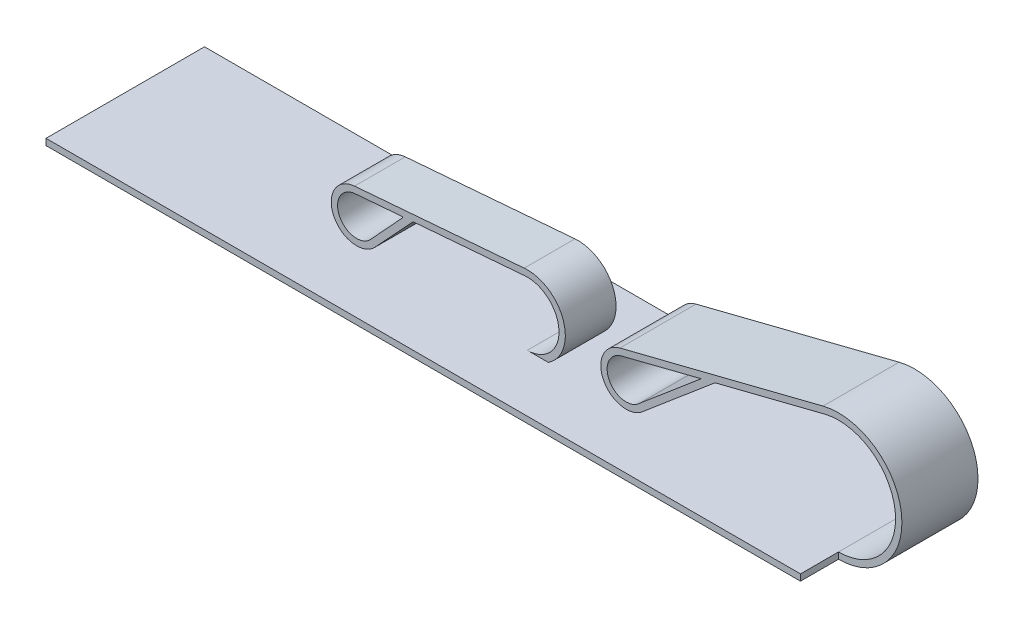
SolidWorks part; units mm, degrees
material "A-Glass Fiber"
ref_plane "Front" through (0, 0, 0) normal (0, 0, 1) x (1, 0, 0)
ref_plane "Top" through (0, 0, 0) normal (0, 1, 0) x (1, 0, 0)
ref_plane "Right" through (0, 0, 0) normal (1, 0, 0) x (0, 0, -1)
sketch "Sketch1" plane through (0, 0, 0) normal (0, 0, 1) x (1, 0, 0)
  line L0 (8.3294, 0) -> (75.2426, 0)
  line L1 (125.1284, 17.7267) -> (107.8556, 13.3703)
  line L2 (74.8373, 9.9835) -> (57.2359, 8.552)
  line L3 (50.5247, 2.7839) -> (55.5536, 8.2411)
  line L4 (95.9369, 4.6002) -> (105.6489, 12.8137)
  line L5 (74.7562, 10.9803) -> (47.9943, 8.8037)
  line L6 (57.2359, 8.552) -> (51.2601, 2.1062)
  line L7 (107.8556, 13.3703) -> (96.6378, 3.887)
  line L8 (8.3294, -1) -> (127.3294, -1)
  line L9 (124.8839, 18.6964) -> (92.8559, 10.6185)
  line L10 (75.2426, 0) -> (78.5593, 0)
  line L11 (127.3294, 0) -> (127.3294, -1)
  line L12 (78.5593, 0) -> (127.3294, 0)
  line L13 (105.6489, 12.8137) -> (93.1005, 9.6489)
  line L15 (55.4719, 8.4085) -> (48.0754, 7.807)
  line L16 (125.1284, 17.7267) -> (93.1005, 9.6489) construction
  line L17 (8.3294, 0) -> (8.3294, -1)
  line L21 (124.8839, 18.6964) -> (92.8559, 10.6185) construction
  arc A0 (127.3294, 0) -> (125.1284, 17.7267) centre (127.3294, 9) ccw
  arc A1 (93.1005, 9.6489) -> (95.9369, 4.6002) centre (93.8341, 6.74) ccw
  arc A2 (75.2426, 0) -> (74.8373, 9.9835) centre (75.2426, 5) ccw
  arc A3 (48.0754, 7.807) -> (50.5247, 2.7839) centre (48.3186, 4.8168) ccw
  arc A4 (47.9943, 8.8037) -> (51.2601, 2.1062) centre (48.3186, 4.8168) ccw
  arc A5 (78.5593, 0) -> (74.7562, 10.9803) centre (75.2426, 5) ccw
  arc A6 (127.3294, -1) -> (124.8839, 18.6964) centre (127.3294, 9) ccw
  arc A7 (92.8559, 10.6185) -> (96.6378, 3.887) centre (93.8341, 6.74) ccw
  arc A8 (55.5536, 8.2411) -> (55.4719, 8.4085) centre (55.48, 8.3089) ccw
  arc A9 (75.2426, -1) -> (74.7562, 10.9803) centre (75.2426, 5) ccw construction
  point P24 (0, 0)
  point P42 (55.727, 8.4293)
  dimension "D2" = 18
  dimension "D3" = 6
  dimension "D4" = 10
  dimension "D5" = 6
  dimension "D6" = 1
  dimension "D8" = 119
  dimension "D7" = 1
  dimension "D10" = 1
  dimension "D11" = 1
extrude "Boss-Extrude1" add sketch "Sketch1" along normal blind 8 from offset 8 contours L9 A7 L7 L1 A0 L12 A5 L5 A4 L6 L2 A2 L0 L17 L8 A6 A8 L3 A3 L15 A1 L13 L4 region at (80.6235, 5.2185, 0)
extrude "Boss-Extrude2" add sketch "Sketch1<5>" along normal blind 12 from offset 7 separate body contours L9 A7 L7 L1 A0 L11 A6 A1 L13 L4 region at (127.8448, -0.5, 0)
sketch "Sketch1<5>" plane through (0, 0, 0) normal (0, 0, 1) x (1, 0, 0) same geometry as "Sketch1"
extrude "Boss-Extrude3" add sketch "Sketch1<6>" along normal blind 25 contours L0 L17 L8 L11 L12 L10 region at (67.8294, -0.5, 0)
sketch "Sketch1<6>" plane through (0, 0, 0) normal (0, 0, 1) x (1, 0, 0) same geometry as "Sketch1"
